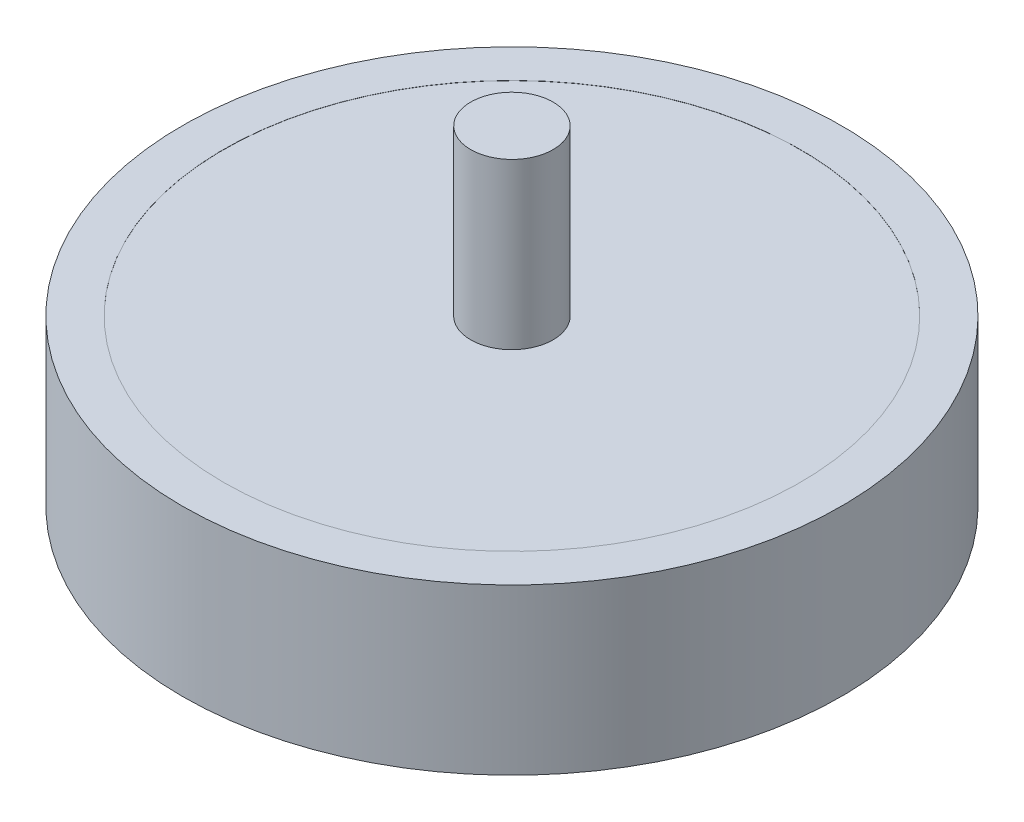
SolidWorks part; units mm, degrees
ref_plane "Front Plane" through (0, 0, 0) normal (0, 0, 1) x (1, 0, 0)
ref_plane "Top Plane" through (0, 0, 0) normal (0, 1, 0) x (1, 0, 0)
ref_plane "Right Plane" through (0, 0, 0) normal (1, 0, 0) x (0, 0, -1)
sketch "Sketch1" plane through (0, 0, 0) normal (0, 1, 0) x (1, 0, 0)
  circle A0 centre (0, 0) radius 20
  circle A1 centre (0, 0) radius 17.5
  dimension "D1" = 40
  dimension "D2" = 35
extrude "Boss-Extrude1" add sketch "Sketch1" along normal blind 10
sketch "Sketch2" plane through (0, 0, 0) normal (0, 1, 0) x (1, 0, 0)
  circle A0 centre (0, 0) radius 17.5
  dimension "D1" = 35
extrude "Boss-Extrude3" add sketch "Sketch2" along normal blind 9.99 separate body
sketch "Sketch3" plane through (0, 0, 0) normal (0, -1, 0) x (1, 0, 0)
  circle A0 centre (0, 0) radius 2.5
  dimension "D1" = 5
sketch "Sketch4" plane through (0, 9.99, 0) normal (0, 1, 0) x (1, 0, 0)
  circle A0 centre (0, 0) radius 2.5
  dimension "D1" = 5
extrude "Boss-Extrude4" add sketch "Sketch4" along normal blind 10
extrude "Cut-Extrude2" cut sketch "Sketch3" against normal blind 5 contours A0
